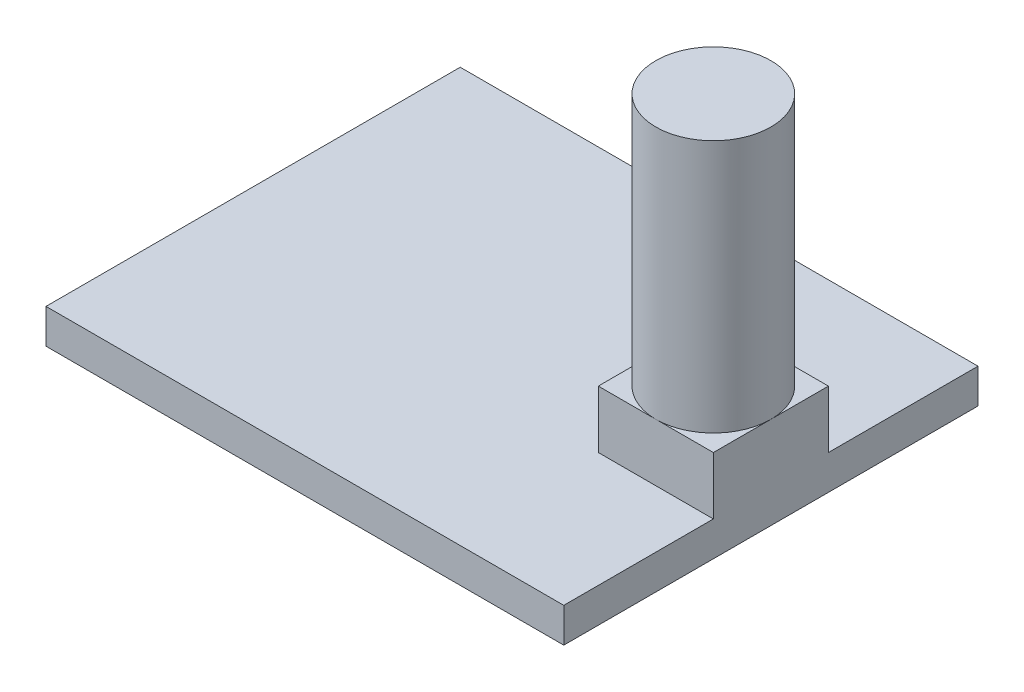
SolidWorks part; units mm, degrees
note: The reader was unsure of these and kept them because the rebuilt part matched: shared geometry of "Sketch2<3>".
ref_plane "前视基准面" through (0, 0, 0) normal (0, 0, 1) x (1, 0, 0)
ref_plane "上视基准面" through (0, 0, 0) normal (0, 1, 0) x (1, 0, 0)
ref_plane "右视基准面" through (0, 0, 0) normal (1, 0, 0) x (0, 0, -1)
sketch "Sketch1" plane through (0, 0, 0) normal (0, 1, 0) x (1, 0, 0)
  line L1 (-22.5, -18) -> (22.5, -18)
  line L2 (-22.5, -18) -> (-22.5, 18)
  line L3 (-22.5, 18) -> (22.5, 18)
  line L4 (22.5, -18) -> (22.5, 18)
  line L5 (-22.5, -18) -> (22.5, 18) construction
  line L6 (-22.5, 18) -> (22.5, -18) construction
  point P0 (0, 0)
  dimension "D1" = 36
  dimension "D2" = 45
extrude "Boss-Extrude1" add sketch "Sketch1" along normal blind 3
sketch "Sketch2" plane through (0, 3, 0) normal (0, 1, 0) x (1, 0, 0)
  line L0 (-23.1171, 0) -> (26.2845, 0) construction
  line L1 (22.5, -18) -> (22.5, 18) construction
  line L2 (22.5, 5) -> (12.5, 5)
  line L3 (22.5, 5) -> (22.5, -5)
  line L4 (22.5, -5) -> (12.5, -5)
  line L5 (12.5, 5) -> (12.5, -5)
  circle A0 centre (17.5, 0) radius 5
  point P11 (0, 0)
  dimension "D3" = 10
  dimension "D1" = 10
  dimension "D2" = 5
extrude "Boss-Extrude2" add sketch "Sketch2" along normal blind 5 contours A0 L0 | L0 A0 | L4 L5 L2 L3
extrude "Boss-Extrude3" add sketch "Sketch2<3>" along normal blind 27 contours A0
sketch "Sketch2<3>" plane through (0, 3, 0) normal (0, 1, 0) x (1, 0, 0) same geometry as "Sketch2"
